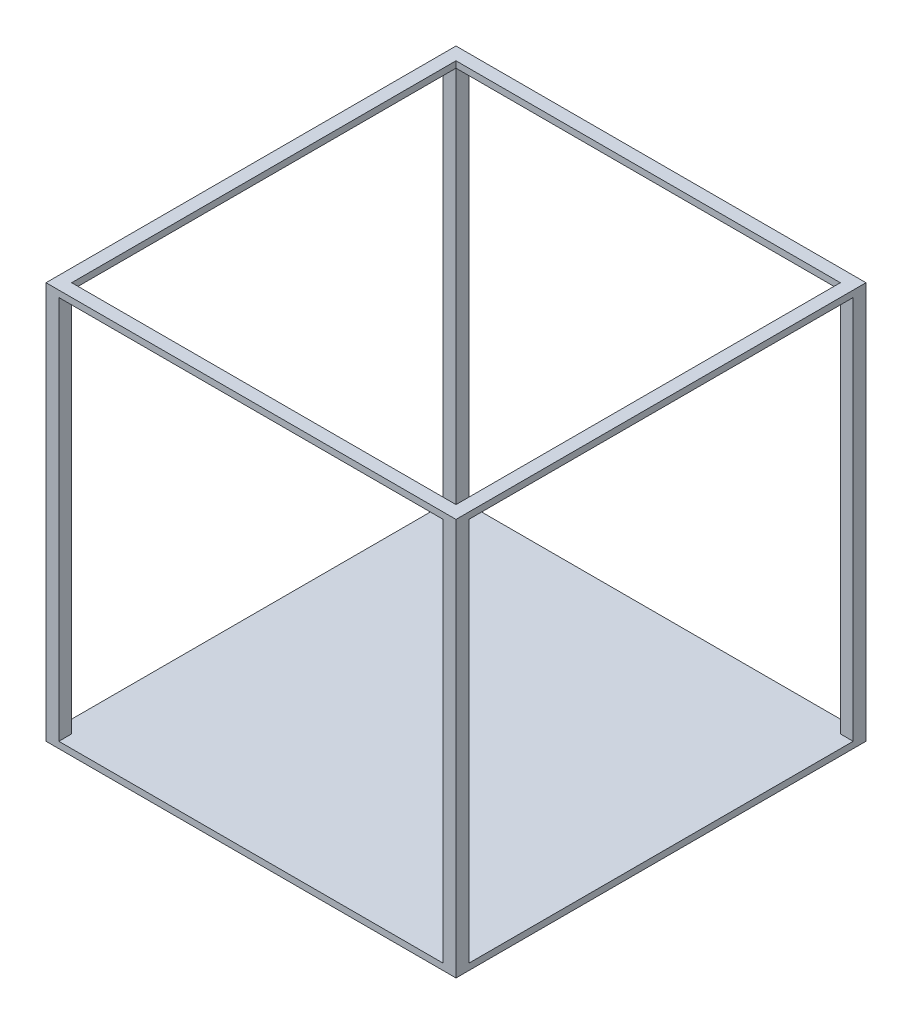
SolidWorks part; units mm, degrees
ref_plane "Front Plane" through (0, 0, 0) normal (0, 0, 1) x (1, 0, 0)
ref_plane "Top Plane" through (0, 0, 0) normal (0, 1, 0) x (1, 0, 0)
ref_plane "Right Plane" through (0, 0, 0) normal (1, 0, 0) x (0, 0, -1)
sketch "Sketch1" plane through (0, 0, 0) normal (0, 1, 0) x (1, 0, 0)
  line L1 (-203.2, -203.2) -> (203.2, -203.2)
  line L2 (-203.2, -203.2) -> (-203.2, 203.2)
  line L3 (-203.2, 203.2) -> (203.2, 203.2)
  line L4 (203.2, -203.2) -> (203.2, 203.2)
  line L5 (-203.2, -203.2) -> (203.2, 203.2) construction
  line L6 (-203.2, 203.2) -> (203.2, -203.2) construction
  point P0 (0, 0)
  dimension "D1" = 406.4
  dimension "D2" = 406.4
extrude "Boss-Extrude1" add sketch "Sketch1" along normal blind 6.35
sketch "Sketch2" plane through (0, 6.35, 0) normal (0, 1, 0) x (1, 0, 0)
  line L0 (0, 203.2) -> (0, -203.2) construction
  line L1 (-203.2, 203.2) -> (-190.5, 203.2)
  line L2 (-203.2, 203.2) -> (-203.2, 190.5)
  line L3 (-203.2, 190.5) -> (-190.5, 190.5)
  line L4 (-190.5, 203.2) -> (-190.5, 190.5)
  line L5 (203.2, 203.2) -> (-203.2, 203.2) construction
  line L6 (-203.2, -203.2) -> (203.2, -203.2) construction
  line L7 (-203.2, 0) -> (203.2, 0) construction
  line L8 (-203.2, 203.2) -> (-203.2, -203.2) construction
  line L9 (203.2, -203.2) -> (203.2, 203.2) construction
  line L10 (190.5, 203.2) -> (190.5, 190.5)
  line L11 (203.2, 190.5) -> (190.5, 190.5)
  line L12 (203.2, 203.2) -> (203.2, 190.5)
  line L13 (203.2, 203.2) -> (190.5, 203.2)
  line L14 (203.2, -203.2) -> (190.5, -203.2)
  line L15 (203.2, -203.2) -> (203.2, -190.5)
  line L16 (203.2, -190.5) -> (190.5, -190.5)
  line L17 (190.5, -203.2) -> (190.5, -190.5)
  line L18 (-190.5, -203.2) -> (-190.5, -190.5)
  line L19 (-203.2, -190.5) -> (-190.5, -190.5)
  line L20 (-203.2, -203.2) -> (-203.2, -190.5)
  line L21 (-203.2, -203.2) -> (-190.5, -203.2)
  dimension "D1" = 12.7
  dimension "D2" = 12.7
extrude "Boss-Extrude2" add sketch "Sketch2" along normal blind 381
sketch "Sketch3" plane through (0, 387.35, 0) normal (0, 1, 0) x (1, 0, 0)
  line L0 (203.2, -190.5) -> (190.5, -190.5) construction
  line L1 (-203.2, 203.2) -> (203.2, 203.2)
  line L2 (-203.2, 203.2) -> (-203.2, -203.2)
  line L3 (-203.2, -203.2) -> (203.2, -203.2)
  line L4 (203.2, 203.2) -> (203.2, -203.2)
  line L5 (-190.5, 190.5) -> (190.5, 190.5)
  line L6 (-190.5, 190.5) -> (-190.5, -190.5)
  line L7 (-190.5, -190.5) -> (190.5, -190.5)
  line L8 (190.5, 190.5) -> (190.5, -190.5)
  line L9 (190.5, -190.5) -> (190.5, -203.2) construction
extrude "Boss-Extrude3" add sketch "Sketch3" along normal blind 6.35
sketch "Sketch4" plane through (0, 6.35, 0) normal (0, 1, 0) x (1, 0, 0)
  line L0 (190.5, -190.5) -> (190.5, -203.2) construction
  line L1 (-190.5, -190.5) -> (190.5, -190.5)
  line L2 (-190.5, -190.5) -> (-190.5, -419.1)
  line L3 (-190.5, -419.1) -> (190.5, -419.1)
  line L4 (190.5, -190.5) -> (190.5, -419.1)
  line L5 (-203.2, 190.5) -> (-190.5, 190.5) construction
  point P5 (185.3342, -190.5)
  point P6 (190.5, -190.5)
  dimension "D1" = 609.6
extrude "Boss-Extrude4" [suppressed] add sketch "Sketch4" against normal blind 6.35
ref_plane "Plane1" through (0, 793.75, 0) normal (0, 1, 0) x (1, 0, 0)
sketch "Sketch5" [suppressed] plane through (0, 793.75, 0) normal (0, 1, 0) x (1, 0, 0)
  line L0 (-190.5, -419.1) -> (190.5, -419.1) construction
  line L1 (-203.2, 203.2) -> (203.2, 203.2)
  line L2 (-203.2, 203.2) -> (-203.2, -431.8)
  line L3 (-203.2, -431.8) -> (203.2, -431.8)
  line L4 (203.2, 203.2) -> (203.2, -431.8)
  line L6 (-190.5, 190.5) -> (190.5, 190.5)
  line L7 (-190.5, 190.5) -> (-190.5, -419.1)
  line L8 (-190.5, -419.1) -> (190.5, -419.1)
  line L9 (190.5, 190.5) -> (190.5, -419.1)
  dimension "D1" = 12.7
extrude "Boss-Extrude5" [suppressed] add sketch "Sketch5" along normal blind 6.35 separate body
